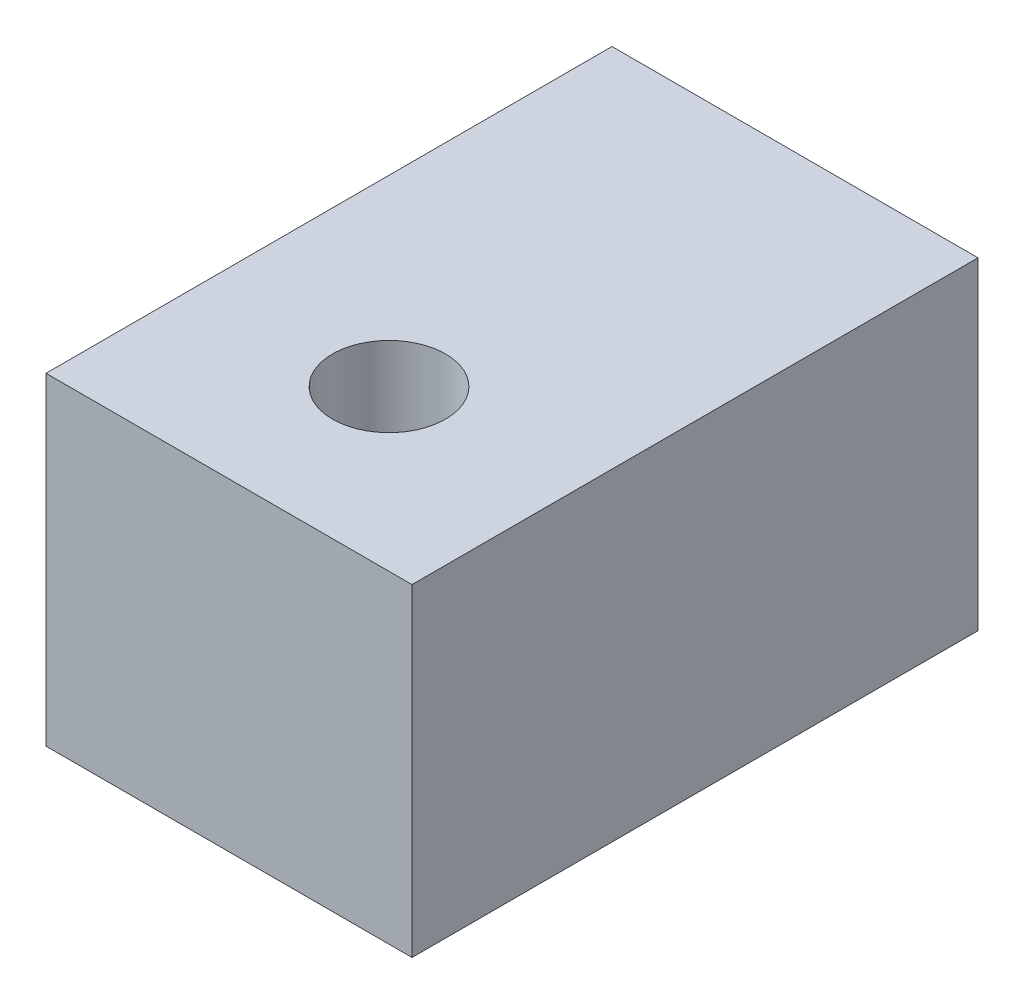
SolidWorks part; units mm, degrees
ref_plane "Front Plane" through (0, 0, 0) normal (0, 0, 1) x (1, 0, 0)
ref_plane "Top Plane" through (0, 0, 0) normal (0, 1, 0) x (1, 0, 0)
ref_plane "Right Plane" through (0, 0, 0) normal (1, 0, 0) x (0, 0, -1)
sketch "Sketch1" plane through (0, 0, 0) normal (0, 0, 1) x (1, 0, 0)
  line L1 (17, -15) -> (-17, -15)
  line L2 (17, -15) -> (17, 15)
  line L3 (17, 15) -> (-17, 15)
  line L4 (-17, -15) -> (-17, 15)
  dimension "D1" = 34
  dimension "D2" = 30
  dimension "D3" = 15
  dimension "D4" = 17
extrude "Boss-Extrude1" add sketch "Sketch1" along normal blind 52.578
sketch "Sketch2" plane through (0, 0, 0) normal (0, 0, -1) x (-1, 0, 0)
  line L0 (-17, -15) -> (-17, 15) construction
  line L1 (17, -15) -> (-17, -15) construction
  circle A4 centre (-12, 9) radius 2 construction
  circle A5 centre (-12, -9) radius 2 construction
  circle A6 centre (12, -9) radius 2 construction
  circle A7 centre (12, 9) radius 2 construction
  circle A8 centre (12, -9) radius 2.1
  circle A9 centre (12, 9) radius 2.1
  circle A10 centre (-12, -9) radius 2.1
  circle A11 centre (-12, 9) radius 2.1
  dimension "D1" = 4
  dimension "D2" = 5
  dimension "D3" = 29
  dimension "D4" = 6
  dimension "D5" = 24
  dimension "D6" = 0.1
extrude "Cut-Extrude1" cut sketch "Sketch2" against normal blind 6
sketch "Sketch5" plane through (0, -15, 0) normal (0, -1, 0) x (1, 0, 0)
  line L0 (17, 52.578) -> (17, 0) construction
  line L1 (-17, 0) -> (17, 0) construction
  circle A1 centre (0, 37.7136) radius 11 construction
  circle A3 centre (0, 37.7136) radius 11.15
  dimension "D1" = 22
  dimension "D2" = 17
  dimension "D3" = 37.7136
  dimension "D4" = 0.15
extrude "Cut-Extrude2" cut sketch "Sketch5" against normal blind 12.5
sketch "Sketch6" plane through (0, 15, 0) normal (0, 1, 0) x (1, 0, 0)
  line L0 (-17, -52.578) -> (-17, 0) construction
  line L1 (17, 0) -> (-17, 0) construction
  circle A1 centre (0, -37.7136) radius 5.1 construction
  circle A2 centre (0, -37.7136) radius 5.25
  dimension "D1" = 10.2
  dimension "D2" = 17
  dimension "D3" = 37.7136
  dimension "D4" = 0.15
extrude "Cut-Extrude3" cut sketch "Sketch6" against normal blind 17.5
sketch "Sketch7" plane through (0, -2.5, 0) normal (0, -1, 0) x (1, 0, 0)
  circle A4 centre (7.9785, 38.3002) radius 1.75 construction
  circle A5 centre (-0.5866, 45.6921) radius 1.75 construction
  circle A6 centre (-7.9785, 37.127) radius 1.75 construction
  circle A7 centre (0.5866, 29.7351) radius 1.75 construction
  circle A8 centre (-7.9785, 37.127) radius 2.1
  circle A9 centre (-0.5866, 45.6921) radius 2.1
  circle A10 centre (7.9785, 38.3002) radius 2.1
  circle A11 centre (0.5866, 29.7351) radius 2.1
  circle A12 centre (0, 37.7136) radius 5.25 construction
  dimension "D2" = 4.2
  dimension "D3" = 0.5866
  dimension "D4" = 7.9785
  dimension "D5" = 0.5866
  dimension "D6" = 7.9785
  dimension "D7" = 0.5866
  dimension "D8" = 7.9785
  dimension "D9" = 0.5866
  dimension "D10" = 7.9785
  dimension "D1" = 0.35
extrude "Cut-Extrude4" cut sketch "Sketch7" against normal blind 6
chamfer "Chamfer1" distance 1 angle 45 4 edges at (7.9785, -2.5, 36.2002) (-0.5866, -2.5, 43.5921) (-7.9785, -2.5, 35.027) (0.5866, -2.5, 27.6351)
chamfer "Chamfer2" distance 1 angle 45 4 edges at (9.9, -9, 0) (-14.1, -9, 0) (-14.1, 9, 0) (9.9, 9, 0)
